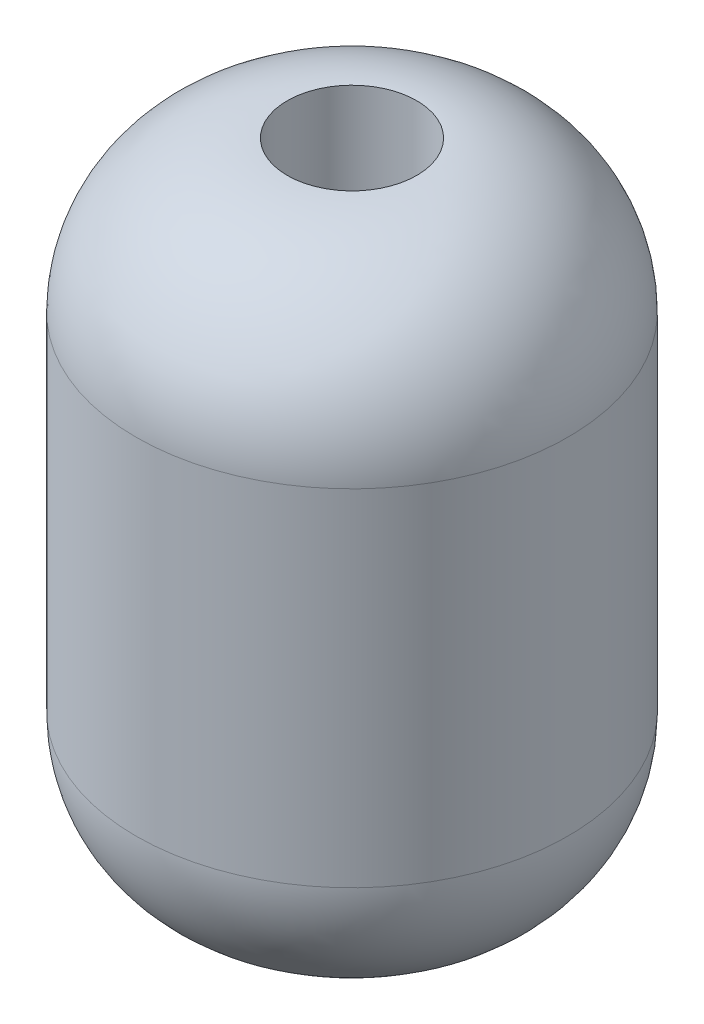
SolidWorks part; units mm, degrees
ref_plane "Plan de face" through (0, 0, 0) normal (0, 0, 1) x (1, 0, 0)
ref_plane "Plan de dessus" through (0, 0, 0) normal (0, 1, 0) x (1, 0, 0)
ref_plane "Plan de droite" through (0, 0, 0) normal (1, 0, 0) x (0, 0, -1)
sketch "Esquisse2" plane through (0, 0, 0) normal (0, 1, 0) x (1, 0, 0)
  circle A0 centre (0, 0) radius 2
  circle A1 centre (0, 0) radius 0.6
extrude "Boss.-Extru.1" add sketch "Esquisse2" along normal blind 6
fillet "Congé1" radius 1.4 2 edges at (0, 0, 2) (0, 6, 2)
